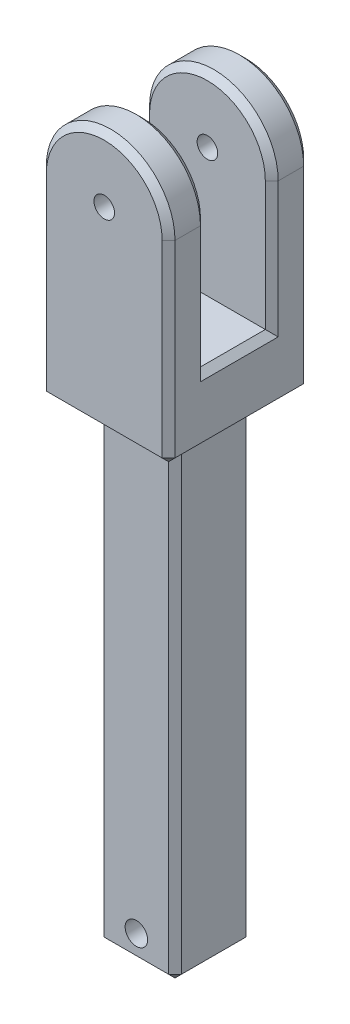
SolidWorks part; units mm, degrees
ref_plane "前基準面" through (0, 0, 0) normal (0, 0, 1) x (1, 0, 0)
ref_plane "上基準面" through (0, 0, 0) normal (0, 1, 0) x (1, 0, 0)
ref_plane "右基準面" through (0, 0, 0) normal (1, 0, 0) x (0, 0, -1)
sketch "草圖1" plane through (0, 0, 0) normal (0, 0, 1) x (1, 0, 0)
  line L0 (0, 0) -> (0, -11.05)
  line L1 (-10, 0) -> (-10, -30.2764)
  line L3 (10, -30.2764) -> (10, 0)
  line L4 (-10, -30.2764) -> (10, -30.2764)
  circle A1 centre (0, 0) radius 1.6
  arc A2 (10, 0) -> (-10, 0) centre (0, 0) ccw
  dimension "D1" = 11.05
  dimension "D2" = 3.2
  dimension "D3" = 20
extrude "填料-伸長1" add sketch "草圖1" along normal blind 12 contours L3 A2 L1 A1 region at (0, -11.2647, 0)
sketch "草圖2" plane through (10, 0, 0) normal (1, 0, 0) x (0, 0, -1)
  line L0 (-12, 0) -> (-9.1, 0)
  line L1 (-12, 0) -> (0, 0) construction
  line L2 (-12, 10) -> (-12, 0) construction
  line L3 (0, 0) -> (-2.9, 0)
  line L4 (-6, 0) -> (-3, 0)
  line L5 (-6, 0) -> (-9, 0)
  line L6 (-9, 0) -> (-9, 15.7808)
  line L7 (-9, 15.7808) -> (-3, 15.7808)
  line L8 (-3, 15.7808) -> (-3, 0)
  line L9 (-3, 0) -> (-3, -20)
  line L10 (-9, 0) -> (-8.6005, -20)
  line L11 (-8.6005, -20) -> (-3, -20)
  line M8 (0, 0) -> (-12, 0)
  dimension "D1" = 2.9
  dimension "D2" = 2.9
  dimension "D3" = 3
  dimension "D4" = 3
  dimension "D5" = 20
extrude "除料-伸長1" cut sketch "草圖2" against normal through all contours L8 L7 L6 M8 | L10 L11 L9 M8 region at (10, 7.8904, 6) region at (10, -9.8852, 5.9013)
sketch "草圖11" plane through (10, 0, 0) normal (1, 0, 0) x (0, 0, -1)
  line L0 (-9, 0) -> (-9, -20)
  line L1 (-9, -20) -> (-8.6005, -20)
  line L2 (-9, 0) -> (-8.6005, -20)
extrude "除料-伸長6" cut sketch "草圖11" against normal through all
sketch "草圖12" plane through (0, 0, 12) normal (0, 0, 1) x (1, 0, 0)
  line L0 (-10, 0) -> (-10, -30.2764)
  line L1 (-10, -30.2764) -> (10, -30.2764)
  line L2 (10, -30.2764) -> (10, 0)
  circle A0 centre (0, 0) radius 1.45
  circle A1 centre (0, 0) radius 10
  circle M1 centre (0, 0) radius 1.6
  line M2 (10, -30.2764) -> (10, 0)
  arc M3 (10, 0) -> (-10, 0) centre (0, 0) ccw
  line M4 (-10, 0) -> (-10, -30.2764)
  line M5 (-10, -30.2764) -> (10, -30.2764)
extrude "填料-伸長11" add sketch "草圖12" along normal blind 5 contours A1 M3 M1 | A1 M4 M5 M2 region at (0, -18.9541, 12) region at (0, 9.7172, 12)
sketch "草圖13" plane through (0, 0, 0) normal (0, 0, -1) x (-1, 0, 0)
  line L0 (-10, 0) -> (-10, -30.2764)
  line L1 (-10, -30.2764) -> (10, -30.2764)
  line L2 (10, 0) -> (10, -30.2764) construction
  line L3 (10, -30.2764) -> (-10, -30.2764) construction
  line L4 (10, -30.2764) -> (10, 0)
  circle A0 centre (0, 0) radius 1.45
  circle A1 centre (0, 0) radius 10
  circle M1 centre (0, 0) radius 1.6
  line M2 (-10, 0) -> (-10, -30.2764)
  line M3 (-10, -30.2764) -> (10, -30.2764)
  line M4 (10, -30.2764) -> (10, 0)
  arc M5 (10, 0) -> (-10, 0) centre (0, 0) ccw
extrude "填料-伸長12" add sketch "草圖13" along normal blind 5 contours A1 M5 M1 | A1 M2 M3 M4 region at (0, -18.9541, 0) region at (0, 9.7172, 0)
sketch "草圖14" plane through (-10, 0, 0) normal (-1, 0, 0) x (0, 0, 1)
  line L0 (3, -20) -> (0.96, -20)
  line L1 (0.96, -20) -> (0.96, 10)
  line L2 (3, 10) -> (-5, 10) construction
  line L3 (0.96, 10) -> (3, 10)
  line L5 (3, 10) -> (11.04, 10)
  line L6 (9, -20) -> (11.04, -20)
  line L7 (11.04, -20) -> (11.04, 10)
  line L8 (17, 10) -> (9, 10) construction
  line L9 (0.96, 10) -> (11.04, 10)
  line L10 (11.04, -20) -> (0.96, -20)
  line L11 (0.96, 10) -> (0.96, -20)
  line L12 (0.96, 10) -> (11.04, 10)
  line M7 (9, 0) -> (9, -20)
  line M8 (9, -20) -> (3, -20)
  line M9 (3, -20) -> (3, 0)
  line M10 (3, 0) -> (-5, 0)
  line M14 (17, 0) -> (9, 0)
  dimension "D1" = 2.04
  dimension "D2" = 2.04
extrude "除料-伸長7" cut sketch "草圖14" against normal through all contours L7 L5 L3 L1 M14 M10 M9 M8 M7 | L1 L0 M9 M10 | L6 L7 M14 M7 region at (-10, -3.1522, 6) region at (-10, -10, 1.98) region at (-10, -10, 10.02)
sketch "草圖15" plane through (0, -30.2764, 0) normal (0, -1, 0) x (1, 0, 0)
  line L0 (-10, 6) -> (10, 6)
  line L1 (-10, 17) -> (-10, -5) construction
  line L2 (10, 17) -> (10, -5) construction
  line L3 (0, 17) -> (0, -5)
  line L4 (-10, 17) -> (10, 17) construction
  line L5 (10, -5) -> (-10, -5) construction
  line L7 (-6, 0) -> (6, 0)
  line L8 (-6, 0) -> (-6, 12)
  line L9 (-6, 12) -> (6, 12)
  line L10 (6, 0) -> (6, 12)
  line L11 (-6, 0) -> (6, 12) construction
  line L12 (-6, 12) -> (6, 0) construction
  point P12 (0, 6)
  dimension "D1" = 12
  dimension "D2" = 12
extrude "填料-伸長13" add sketch "草圖15" along normal blind 74 contours L0 L10 L9 L3 | L9 L8 L0 L3 | L7 L10 L0 L3 | L8 L7 L3 L0 region at (-3, -30.2764, 9) region at (-3, -30.2764, 3) region at (3, -30.2764, 9) region at (3, -30.2764, 3)
sketch "草圖17" plane through (0, 0, 0) normal (0, 0, -1) x (-1, 0, 0)
  line L0 (0, -104.2764) -> (0, -100.2764)
  line L1 (6, -104.2764) -> (-6, -104.2764) construction
  circle A0 centre (0, -100.2764) radius 1.75
  dimension "D2" = 3.5
  dimension "D1" = 4
extrude "除料-伸長8" cut sketch "草圖17" against normal through all contours A0 region at (-1.2024, -101.4789, 0)
chamfer "導角1" distance 1 angle 45 30 edges at (-10, -10, 0.96) (-10, -10, 11.04) (-10, -20, 6) (0, 10, 0.96) (0, 10, 11.04) (10, -10, 0.96) (10, -10, 11.04) (10, -20, 6) (0, 10, -5) (0, 10, 17) (10, -30.2764, 6) (10, -15.1382, -5) (0, -30.2764, -5) (10, -15.1382, 17) (-10, -15.1382, -5) (-10, -30.2764, 6) (-10, -15.1382, 17) (0, -30.2764, 17) (6, -30.2764, 6) (0, -30.2764, 12) (0, -30.2764, 0) (-6, -67.2764, 12) (-6, -104.2764, 6) (-6, -30.2764, 6) (-6, -67.2764, 0) (0, -104.2764, 0) (0, -104.2764, 12) (6, -67.2764, 12) (6, -104.2764, 6) (6, -67.2764, 0)
